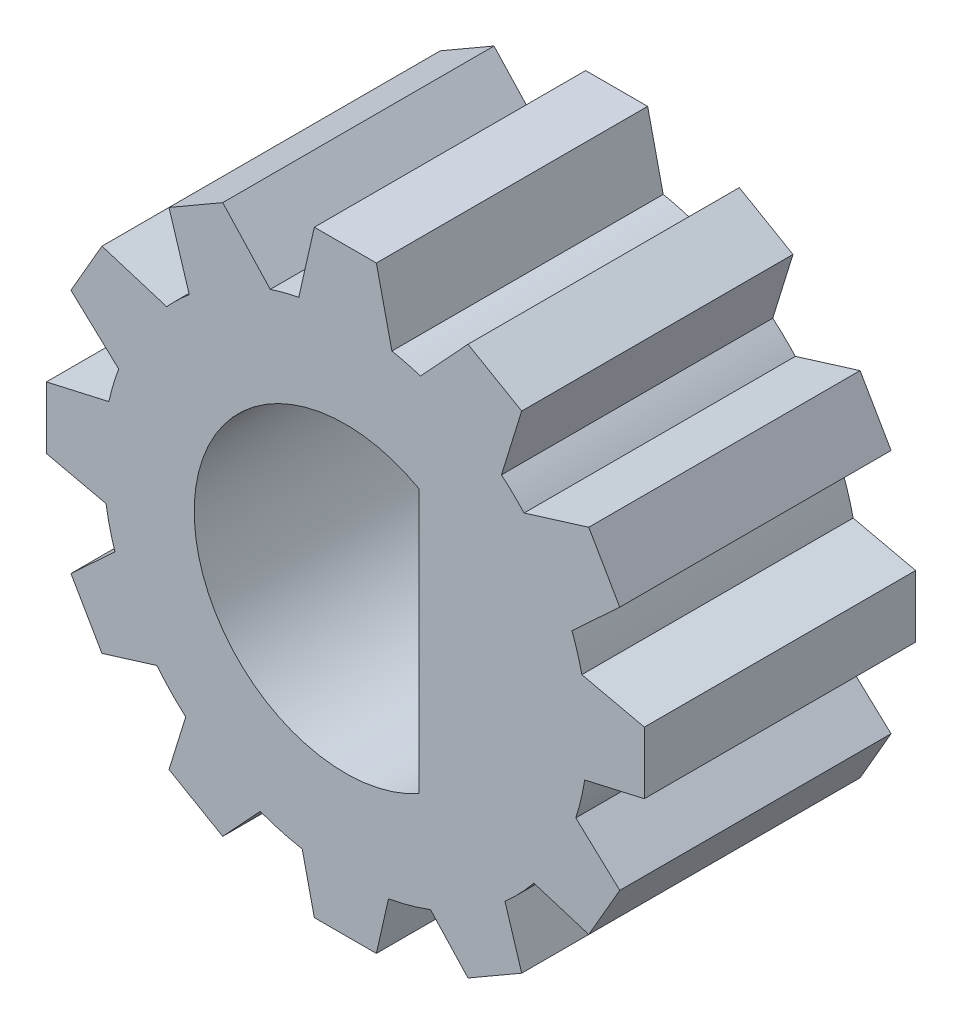
SolidWorks part; units mm, degrees
note: '?' marks a value the reader was unsure of.
ref_plane "Front Plane" through (0, 0, 0) normal (0, 0, 1) x (1, 0, 0)
ref_plane "Top Plane" through (0, 0, 0) normal (0, 1, 0) x (1, 0, 0)
ref_plane "Right Plane" through (0, 0, 0) normal (1, 0, 0) x (0, 0, -1)
sketch "Sketch1" plane through (0, 0, 0) normal (0, 0, 1) x (1, 0, 0)
  circle A0 centre (0, 0) radius 6.25
  dimension "D1" = 12.5
extrude "Boss-Extrude1" add sketch "Sketch1" along normal blind 7
sketch "Sketch3" plane through (0, 0, 0) normal (0, 0, 1) x (1, 0, 0)
  line L0 (0, -7.9) -> (0, 7.9) construction
  line L1 (-0.8, 7.9) -> (0.8, 7.9)
  line L2 (-0.8, 7.9) -> (-1.3, 5.7)
  line L3 (-1.3, 5.7) -> (1.3, 5.7)
  line L4 (1.3, 5.7) -> (0.8, 7.9)
  point P3 (0, 0)
  point P4 (0, 5.7)
  point P6 (0, 7.9)
  dimension "D1" = 7.9
  dimension "D2" = 2.6
  dimension "D3" = 1.6
  dimension "D4" = 5.7
extrude "Boss-Extrude2" add sketch "Sketch3" along normal blind 7
ref_axis "Axis2" through (0, 0, 7) along (0, 0, -1)?
pattern_circular "CirPattern1" count 12 every 30 about axis through (0, 0.186, 0) along (0, 0, 1) of "Boss-Extrude2"
sketch "Sketch4" plane through (0, 0, 0) normal (0, 0, 1) x (1, 0, 0)
  line L0 (1.9, 3.4059) -> (1.9, -3.4059)
  arc A0 (1.9, 3.4059) -> (1.9, -3.4059) centre (0, 0) ccw
  dimension "D1" = 7.8
  dimension "D2" = 1.9
extrude "Cut-Extrude1" cut sketch "Sketch4" along normal blind 7
